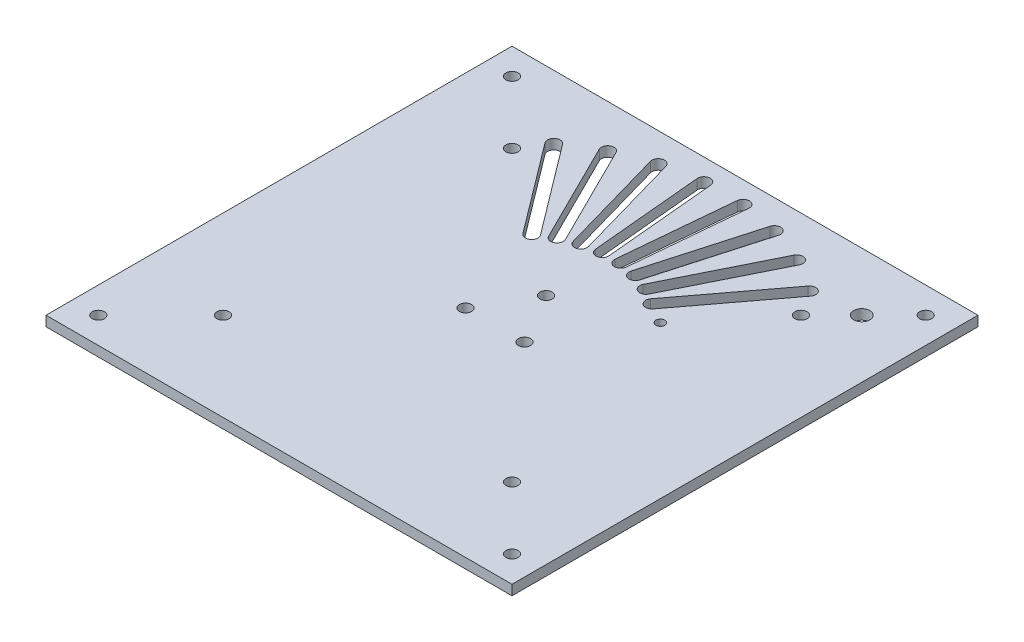
SolidWorks part; units mm, degrees
material "Acrylic (Medium-high impact)"
ref_plane "Front Plane" through (0, 0, 0) normal (0, 0, 1) x (1, 0, 0)
ref_plane "Top Plane" through (0, 0, 0) normal (0, 1, 0) x (1, 0, 0)
ref_plane "Right Plane" through (0, 0, 0) normal (1, 0, 0) x (0, 0, -1)
sketch "Sketch2" plane through (0, 0, 0) normal (0, 1, 0) x (1, 0, 0)
  line L1 (-65, -65) -> (65, -65)
  line L2 (-65, -65) -> (-65, 65)
  line L3 (-65, 65) -> (65, 65)
  line L4 (65, -65) -> (65, 65)
  line L5 (-65, -65) -> (65, 65) construction
  line L6 (-65, 65) -> (65, -65) construction
  point P0 (0, 0)
  dimension "D1" = 130
  dimension "D2" = 130
extrude "Boss-Extrude1" add sketch "Sketch2" along normal blind 2.8
sketch "Sketch4" plane through (0, 2.8, 0) normal (0, 1, 0) x (1, 0, 0)
  line L8 (57.7, -57.7) -> (57.7, 57.7)
  line L9 (57.7, 57.7) -> (-57.7, 57.7)
  line L10 (-57.7, 57.7) -> (-57.7, -57.7)
  line L11 (-57.7, -57.7) -> (57.7, -57.7)
  line L12 (57.7, -57.7) -> (57.7, 57.7) construction
  line L13 (57.7, 57.7) -> (-57.7, 57.7) construction
  line L14 (-57.7, 57.7) -> (-57.7, -57.7) construction
  line L15 (-57.7, -57.7) -> (57.7, -57.7) construction
  circle A0 centre (-57.7, 57.7) radius 1.7
  circle A1 centre (57.7, 57.7) radius 1.7
  circle A2 centre (57.7, -57.7) radius 1.7
  circle A3 centre (-57.7, -57.7) radius 1.7
  dimension "D2" = 3.4
  dimension "D1" = 7.3
extrude "Cornerpiece holes" cut sketch "Sketch4" against normal up to next
sketch "Sketch6" plane through (0, 2.8, 0) normal (0, 1, 0) x (1, 0, 0)
  line L6 (-40.3051, -40.3051) -> (40.3051, -40.3051) construction
  line L7 (-40.3051, -40.3051) -> (-40.3051, 40.3051) construction
  line L8 (-40.3051, 40.3051) -> (40.3051, 40.3051) construction
  line L9 (40.3051, -40.3051) -> (40.3051, 40.3051) construction
  line L10 (-40.3051, -40.3051) -> (40.3051, 40.3051) construction
  line L11 (-40.3051, 40.3051) -> (40.3051, -40.3051) construction
  circle A4 centre (-40.3051, 40.3051) radius 1.7
  circle A5 centre (40.3051, 40.3051) radius 1.7
  circle A6 centre (40.3051, -40.3051) radius 1.7
  circle A7 centre (-40.3051, -40.3051) radius 1.7
  point P0 (0, 0)
  dimension "D2" = 3.4
  dimension "D1" = 57
extrude "Cut-Extrude2" cut sketch "Sketch6" against normal up to next
sketch "Sketch8" plane through (0, 2.8, 0) normal (0, 1, 0) x (1, 0, 0)
  circle A4 centre (0, 9.5) radius 1.7
  circle A5 centre (8.2272, -4.75) radius 1.7
  circle A6 centre (-8.2272, -4.75) radius 1.7
  point P9 (0, 0)
  dimension "D1" = 9.5
  dimension "D3" = 3.4
  dimension "D2" = 3
extrude "Cut-Extrude3" cut sketch "Sketch8" against normal up to next
sketch "Sketch9" plane through (0, 2.8, 0) normal (0, 1, 0) x (1, 0, 0)
  line L0 (65, -65) -> (65, 65) construction
  line L1 (48.7904, 48.7904) -> (0, 0) construction
  line L2 (0, 0) -> (50000, 0) construction
  circle A0 centre (0, 0) radius 65 construction
  circle A1 centre (48.7904, 48.7904) radius 2.25
  dimension "D3" = 4
  dimension "D1" = 4.5
  dimension "D2" = 45
extrude "Primary wire hole" cut sketch "Sketch9" against normal up to next
sketch "Sketch10" plane through (0, 2.8, 0) normal (0, 1, 0) x (1, 0, 0)
  line L0 (0, 0) -> (22.5064, 18.8851) construction
  line L1 (0, 0) -> (50000, 0) construction
  circle A0 centre (0, 0) radius 24.13 construction
  circle A1 centre (22.5064, 18.8851) radius 1.25
  dimension "D1" = 48.26
  dimension "D3" = 2.5
  dimension "D2" = 40
  dimension "D4" = 4
extrude "Secondary wire hole" cut sketch "Sketch10" against normal up to next
sketch "Sketch11" plane through (0, 2.8, 0) normal (0, 1, 0) x (1, 0, 0)
  line L0 (-35.6575, 47.3192) -> (-16.7786, 22.266) construction
  line L1 (-34.2599, 48.3723) -> (-15.381, 23.3191)
  line L2 (-37.0552, 46.266) -> (-18.1762, 21.2128)
  line L3 (0, 0) -> (-16.7786, 22.266) construction
  line L4 (-27.9382, 52.2789) -> (-13.976, 24.1874)
  line L5 (-24.804, 53.8367) -> (-10.8418, 25.7452)
  line L6 (-26.3711, 53.0578) -> (-12.4089, 24.9663) construction
  line L7 (-17.8729, 56.5171) -> (-9.3013, 26.3409)
  line L8 (-14.5061, 57.4735) -> (-5.9345, 27.2972)
  line L9 (-16.1895, 56.9953) -> (-7.6179, 26.8191) construction
  line L10 (-7.2008, 58.8368) -> (-4.3109, 27.6002)
  line L11 (-3.7157, 59.1593) -> (-0.8258, 27.9227)
  line L12 (-5.4582, 58.9981) -> (-2.5684, 27.7614) construction
  line L13 (3.7157, 59.1593) -> (0.8258, 27.9227)
  line L14 (7.2008, 58.8368) -> (4.3109, 27.6002)
  line L15 (5.4582, 58.9981) -> (2.5684, 27.7614) construction
  line L18 (0, 0) -> (50000, 0) construction
  line L19 (14.5061, 57.4735) -> (5.9345, 27.2972)
  line L20 (17.8729, 56.5171) -> (9.3013, 26.3409)
  line L21 (16.1895, 56.9953) -> (7.6179, 26.8191) construction
  line L22 (24.804, 53.8367) -> (10.8418, 25.7452)
  line L23 (27.9382, 52.2789) -> (13.976, 24.1874)
  line L24 (26.3711, 53.0578) -> (12.4089, 24.9663) construction
  line L25 (34.2599, 48.3723) -> (15.381, 23.3191)
  line L26 (37.0552, 46.266) -> (18.1762, 21.2128)
  line L27 (35.6575, 47.3192) -> (16.7786, 22.266) construction
  line L28 (0, 0) -> (16.7786, 22.266) construction
  circle A0 centre (0, 0) radius 24.13 construction
  circle A1 centre (0, 0) radius 63 construction
  arc A2 (-34.2599, 48.3723) -> (-37.0552, 46.266) centre (-35.6575, 47.3192) ccw
  arc A3 (-18.1762, 21.2128) -> (-15.381, 23.3191) centre (-16.7786, 22.266) ccw
  arc A4 (-24.804, 53.8367) -> (-27.9382, 52.2789) centre (-26.3711, 53.0578) ccw
  arc A5 (-13.976, 24.1874) -> (-10.8418, 25.7452) centre (-12.4089, 24.9663) ccw
  arc A6 (-14.5061, 57.4735) -> (-17.8729, 56.5171) centre (-16.1895, 56.9953) ccw
  arc A7 (-9.3013, 26.3409) -> (-5.9345, 27.2972) centre (-7.6179, 26.8191) ccw
  arc A8 (-3.7157, 59.1593) -> (-7.2008, 58.8368) centre (-5.4582, 58.9981) ccw
  arc A9 (-4.3109, 27.6002) -> (-0.8258, 27.9227) centre (-2.5684, 27.7614) ccw
  arc A10 (7.2008, 58.8368) -> (3.7157, 59.1593) centre (5.4582, 58.9981) ccw
  arc A11 (0.8258, 27.9227) -> (4.3109, 27.6002) centre (2.5684, 27.7614) ccw
  arc A14 (17.8729, 56.5171) -> (14.5061, 57.4735) centre (16.1895, 56.9953) ccw
  arc A15 (5.9345, 27.2972) -> (9.3013, 26.3409) centre (7.6179, 26.8191) ccw
  arc A16 (27.9382, 52.2789) -> (24.804, 53.8367) centre (26.3711, 53.0578) ccw
  arc A17 (10.8418, 25.7452) -> (13.976, 24.1874) centre (12.4089, 24.9663) ccw
  arc A18 (37.0552, 46.266) -> (34.2599, 48.3723) centre (35.6575, 47.3192) ccw
  arc A19 (15.381, 23.3191) -> (18.1762, 21.2128) centre (16.7786, 22.266) ccw
  point P6 (-26.2181, 34.7926)
  point P17 (-19.39, 39.012)
  point P24 (-11.9037, 41.9072)
  point P31 (-4.0133, 43.3797)
  point P36 (0, 0)
  point P38 (4.0133, 43.3797)
  point P48 (11.9037, 41.9072)
  point P55 (19.39, 39.012)
  point P62 (26.2181, 34.7926)
  dimension "D1" = 48.26
  dimension "D2" = 126
  dimension "D4" = 2
  dimension "D5" = 3.5
  dimension "D7" = 53
  dimension "D8" = 53
  dimension "D6" = 8
extrude "Cut-Extrude6" cut sketch "Sketch11" against normal up to next
equation "\"D1@Sketch4\"=4.50+2.8"
equation "\"D1@Sketch10\"=1.9in"
equation "\"D1@Sketch11\"=1.9in"
equation "\"D2@Sketch11\"=130mm-2*2mm"
